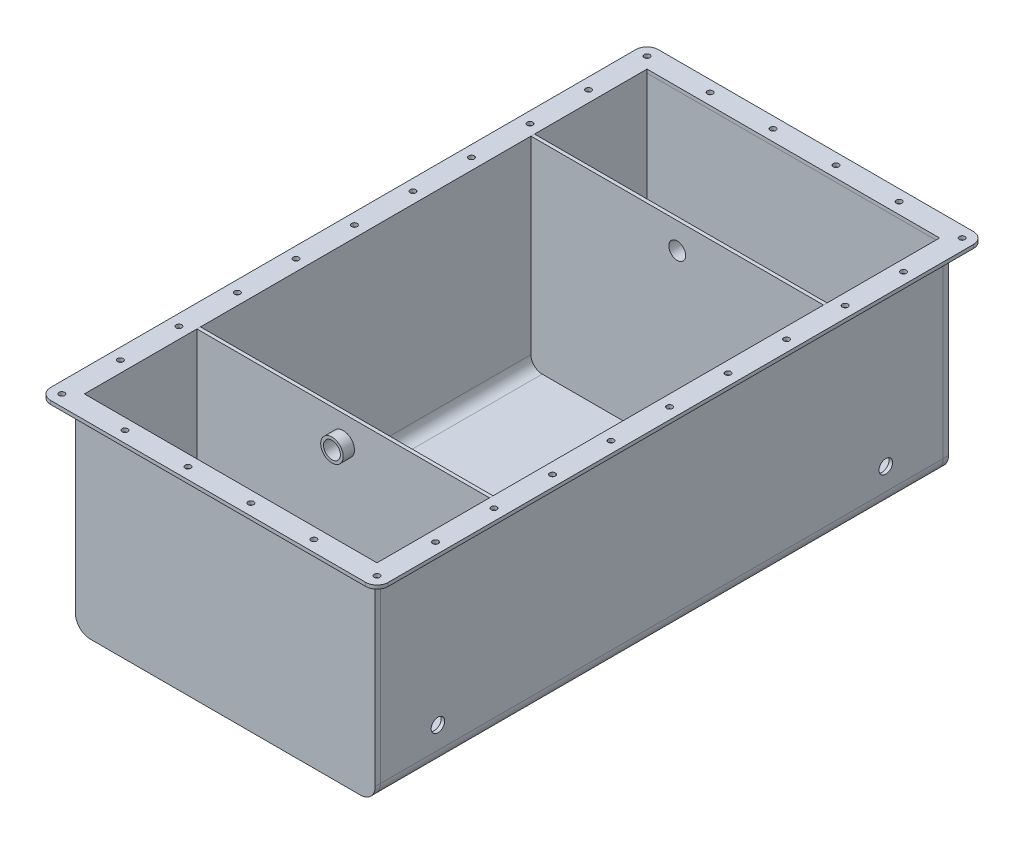
SolidWorks part; units mm, degrees
material "5052-H32"
ref_plane "Front Plane" through (0, 0, 0) normal (0, 0, 1) x (1, 0, 0)
ref_plane "Top Plane" through (0, 0, 0) normal (0, 1, 0) x (1, 0, 0)
ref_plane "Right Plane" through (0, 0, 0) normal (1, 0, 0) x (0, 0, -1)
sketch "Sketch2" plane through (0, 0, 0) normal (0, 0, 1) x (1, 0, 0)
  line L0 (-130, 0) -> (130, 0)
  line L1 (-130, 0) -> (-130, 175)
  line L2 (130, 0) -> (130, 175)
  line L3 (-133.175, -3.175) -> (-133.175, 175)
  line L4 (-133.175, -3.175) -> (133.175, -3.175)
  line L5 (133.175, -3.175) -> (133.175, 175)
  line L6 (-133.175, 175) -> (-130, 175)
  line L7 (130, 175) -> (133.175, 175)
  point P4 (0, 0)
  dimension "D1" = 260
  dimension "D3" = 175
  dimension "D4" = 175
  dimension "D2" = 3.175
  dimension "D5" = 3.175
  dimension "D6" = 3.175
extrude "Interior Dim" add sketch "Sketch2" against normal blind 500
fillet "Fillet2" radius 10 2 edges at (-130, 0, -250) (130, 0, -250)
fillet "Fillet3" radius 13.175 2 edges at (-133.175, -3.175, -250) (133.175, -3.175, -250)
ref_plane "Plane1" through (0, 0, 0) normal (0, 0, 1) x (1, 0, 0)
sketch "Sketch4" plane through (0, 0, 0) normal (0, 0, 1) x (1, 0, 0)
  line L0 (-130, 175) -> (130, 175)
  line L9 (-120, -3.175) -> (120, -3.175)
  line L10 (133.175, 10) -> (133.175, 175)
  line L11 (133.175, 175) -> (130, 175)
  line L12 (130, 175) -> (130, 10)
  line L13 (120, 0) -> (-120, 0)
  line L14 (-130, 10) -> (-130, 175)
  line L15 (-130, 175) -> (-133.175, 175)
  line L16 (-133.175, 175) -> (-133.175, 10)
  line L17 (-120, -3.175) -> (120, -3.175)
  line L18 (133.175, 10) -> (133.175, 175)
  line L19 (133.175, 175) -> (130, 175)
  line L23 (-130, 175) -> (-133.175, 175)
  line L24 (-133.175, 175) -> (-133.175, 10)
  arc A4 (120, -3.175) -> (133.175, 10) centre (120, 10) ccw
  arc A5 (120, 0) -> (130, 10) centre (120, 10) ccw
  arc A6 (-130, 10) -> (-120, 0) centre (-120, 10) ccw
  arc A7 (120, -3.175) -> (133.175, 10) centre (120, 10) ccw
  arc A9 (-133.175, 10) -> (-120, -3.175) centre (-120, 10) ccw
  arc A10 (-133.175, 10) -> (-120, -3.175) centre (-120, 10) ccw
  dimension "D1" = 0
extrude "Endcap1" add sketch "Sketch4" along normal blind 4.7625 separate body
ref_plane "Plane2" through (0, 0, -500) normal (0, 0, -1) x (-1, 0, 0)
sketch "Sketch5" plane through (0, 0, -500) normal (0, 0, -1) x (-1, 0, 0)
  line L8 (133.175, 175) -> (-133.175, 175)
  line L16 (-133.175, 175) -> (-133.175, 10)
  line L17 (-120, -3.175) -> (120, -3.175)
  line L18 (133.175, 10) -> (133.175, 175)
  line L19 (133.175, 175) -> (130, 175)
  line L20 (130, 175) -> (130, 10)
  line L21 (120, 0) -> (-120, 0)
  line L22 (-130, 10) -> (-130, 175)
  line L23 (-130, 175) -> (-133.175, 175)
  line L24 (-133.175, 175) -> (-133.175, 10)
  line L25 (-120, -3.175) -> (120, -3.175)
  line L26 (133.175, 10) -> (133.175, 175)
  arc A6 (-133.175, 10) -> (-120, -3.175) centre (-120, 10) ccw
  arc A7 (-133.175, 10) -> (-120, -3.175) centre (-120, 10) ccw
  arc A8 (120, 0) -> (130, 10) centre (120, 10) ccw
  arc A9 (-130, 10) -> (-120, 0) centre (-120, 10) ccw
  arc A12 (120, -3.175) -> (133.175, 10) centre (120, 10) ccw
  arc A13 (120, -3.175) -> (133.175, 10) centre (120, 10) ccw
  dimension "D1" = 0
ref_plane "Compartment1" through (0, 0, -100) normal (0, 0, -1) x (-1, 0, 0)
sketch "Sketch7" plane through (0, 0, -100) normal (0, 0, -1) x (-1, 0, 0)
  line L1 (130, 175) -> (-130, 175)
  line L10 (-120, -3.175) -> (120, -3.175)
  line L11 (-133.175, 175) -> (-133.175, 10)
  line L12 (-130, 175) -> (-133.175, 175)
  line L13 (-130, 10) -> (-130, 175)
  line L14 (120, 0) -> (-120, 0)
  line L15 (130, 175) -> (130, 10)
  line L16 (133.175, 175) -> (130, 175)
  line L17 (133.175, 10) -> (133.175, 175)
  line L21 (-130, 10) -> (-130, 175)
  line L22 (120, 0) -> (-120, 0)
  line L23 (130, 175) -> (130, 10)
  arc A5 (-130, 10) -> (-120, 0) centre (-120, 10) ccw
  arc A6 (120, 0) -> (130, 10) centre (120, 10) ccw
  arc A7 (-133.175, 10) -> (-120, -3.175) centre (-120, 10) ccw
  arc A8 (120, -3.175) -> (133.175, 10) centre (120, 10) ccw
  arc A9 (-130, 10) -> (-120, 0) centre (-120, 10) ccw
  arc A10 (120, 0) -> (130, 10) centre (120, 10) ccw
  dimension "D1" = 0
extrude "Compartment1_Boss" add sketch "Sketch7" along normal blind 3.175 separate body contours L22 A10 L23 L1 L21 A9 region at (0, 87.5805, -100)
ref_plane "Plane5" through (0, 175, 0) normal (0, 1, 0) x (1, 0, 0)
sketch "Sketch9" plane through (0, 175, 0) normal (0, 1, 0) x (1, 0, 0)
  line L0 (97.9962, 500) -> (-97.9962, 500) construction
  line L1 (-130, 500) -> (130, 500)
  line L2 (-130, 500) -> (-130, 0)
  line L3 (-130, 0) -> (130, 0)
  line L4 (130, 500) -> (130, 0)
  line L5 (-130, 0) -> (-130, 500) construction
  line L6 (-97.9962, 0) -> (97.9962, 0) construction
  line L7 (130, 500) -> (130, 0) construction
  line L8 (-150, 520) -> (-150, -20)
  line L9 (-150, -20) -> (150, -20)
  line L10 (150, 520) -> (150, -20)
  line L11 (-150, 520) -> (150, 520)
  circle A0 centre (-140, -10) radius 2.5
  circle A2 centre (-140, 42) radius 2.5
  circle A3 centre (-140, 94) radius 2.5
  circle A4 centre (-140, 146) radius 2.5
  circle A5 centre (-140, 198) radius 2.5
  circle A6 centre (-140, 250) radius 2.5
  circle A7 centre (-140, 302) radius 2.5
  circle A8 centre (-140, 354) radius 2.5
  circle A9 centre (-140, 406) radius 2.5
  circle A10 centre (-140, 458) radius 2.5
  circle A16 centre (-140, 510) radius 2.5
  circle A17 centre (-84, 510) radius 2.5
  circle A18 centre (-28, 510) radius 2.5
  circle A19 centre (28, 510) radius 2.5
  circle A20 centre (84, 510) radius 2.5
  circle A21 centre (140, 510) radius 2.5
  circle A22 centre (140, 458) radius 2.5
  circle A23 centre (140, 406) radius 2.5
  circle A24 centre (140, 354) radius 2.5
  circle A25 centre (140, 302) radius 2.5
  circle A26 centre (140, 250) radius 2.5
  circle A27 centre (140, 198) radius 2.5
  circle A28 centre (140, 146) radius 2.5
  circle A29 centre (140, 94) radius 2.5
  circle A30 centre (140, 42) radius 2.5
  circle A31 centre (140, -10) radius 2.5
  circle A37 centre (84, -10) radius 2.5
  circle A38 centre (28, -10) radius 2.5
  circle A39 centre (-28, -10) radius 2.5
  circle A40 centre (-84, -10) radius 2.5
  dimension "D4" = 5
  dimension "D7" = 5
  dimension "D2" = 10
  dimension "D3" = 10
  dimension "D5" = 6
  dimension "D6" = 11
  dimension "D8" = 11
  dimension "D1" = 20
extrude "Lid_Flange" add sketch "Sketch9" along normal blind 3.175 separate body contours L11 L8 L9 L10 A31 A21 A20 A19 A18 A17 A16 A10 A9 A8 A7 A6 A5 A4 A3 A2 A0 L1 L4 region at (0, 175, -513.8226)
fillet "Fillet4" radius 10 4 edges at (-150, 176.5875, -520) (150, 176.5875, -520) (150, 176.5875, 20) (-150, 176.5875, 20)
extrude "Endcap2" add sketch "Sketch5" along normal blind 4.7625 separate body
ref_plane "Compartment2" through (0, 0, -400) normal (0, 0, 1) x (1, 0, 0)
sketch "Sketch13" plane through (0, 0, -400) normal (0, 0, 1) x (1, 0, 0)
  line L0 (130, 175) -> (-130, 175)
  line L1 (133.175, 175) -> (130, 175) construction
  line L2 (130, 175) -> (130, 10) construction
  line L3 (-140, 175) -> (140, 175) construction
  line L4 (-130, 10) -> (-130, 175) construction
  line L5 (130, 175) -> (130, 10)
  line L6 (-130, 175) -> (-130, 10)
  line L7 (120, 0) -> (-120, 0)
  arc A0 (120, 0) -> (130, 10) centre (120, 10) ccw construction
  arc A1 (-130, 10) -> (-120, 0) centre (-120, 10) ccw construction
  arc A2 (-130, 10) -> (-120, 0) centre (-120, 10) ccw
  arc A3 (130, 10) -> (120, 0) centre (120, 10) cw
  dimension "D1" = 175
extrude "Compartment2_Boss" add sketch "Sketch13" along normal blind 3.175
sketch "Sketch16" plane through (-133.175, 0, 0) normal (-1, 0, 0) x (0, 0, 1)
  line L0 (-500, 0) -> (-400, 0) construction
  line L1 (-500, 175) -> (-500, 10) construction
  line L2 (0, 175) -> (0, 10) construction
  line L3 (-51, 29.5) -> (-449, 29.5) construction
  circle A0 centre (-449, 29.5) radius 6
  circle A1 centre (-51, 29.5) radius 6
  dimension "D1" = 12
  dimension "D4" = 12
  dimension "D2" = 29.5
  dimension "D3" = 51
  dimension "D5" = 51
extrude "Bearing_holes" cut sketch "Sketch16" against normal through all
sketch "Sketch17" plane through (0, 0, -400) normal (0, 0, -1) x (-1, 0, 0)
  line L0 (142.7388, 175) -> (-142.7388, 175) construction
  line L1 (130, 175) -> (130, 10) construction
  circle A0 centre (0, 155) radius 7.5
  circle A1 centre (0, 155) radius 10
  dimension "D1" = 15
  dimension "D4" = 20
  dimension "D2" = 20
  dimension "D3" = 130
extrude "Wire_Passthrough" cut sketch "Sketch17" against normal up to surface (300 mm away) contours A0 region at (0, 155, -400) up to face at (0, 60.9763, -100)
sketch "Sketch18" plane through (0, 175, 0) normal (0, 1, 0) x (1, 0, 0)
  line L1 (-130, 400) -> (130, 400)
  line L2 (-130, 400) -> (-130, 396.825)
  line L3 (-130, 396.825) -> (130, 396.825)
  line L4 (130, 400) -> (130, 396.825)
  line L5 (-130, 103.175) -> (130, 103.175)
  line L6 (-130, 103.175) -> (-130, 100)
  line L7 (-130, 100) -> (130, 100)
  line L8 (130, 103.175) -> (130, 100)
extrude "Boss-Extrude1" add sketch "Sketch18" along normal blind 3.18
extrude "Wire_Tube_2" add sketch "Sketch17<3>" along normal blind 10
sketch "Sketch17<3>" plane through (0, 0, -400) normal (0, 0, -1) x (-1, 0, 0) same geometry as "Sketch17"
sketch "Sketch19" plane through (0, 0, -100) normal (0, 0, 1) x (1, 0, 0)
  circle A0 centre (0, 155) radius 10
  circle M1 centre (0, 155) radius 7.5
  dimension "D1" = 20
extrude "Wire_Tube_1" add sketch "Sketch19" along normal blind 10 contours A0 M1 region at (-9.7172, 155, -100)
equation "\"L\"= 500"
equation "\"W\"= 260"
equation "\"D1@Sketch2\"=\"W\""
equation "\"D1@Interior Dim\" = \"L\""
equation "\"H\"= 175"
equation "\"D3@Sketch2\"=\"H\""
equation "\"D4@Sketch2\"=\"H\""
equation "\"Compartment Width\"= 100"
equation "\"D1@Compartment2\"=\"Compartment Width\""
equation "\"D1@Compartment1\"=\"Compartment Width\""
equation "\"D1@Sketch13\"=\"H\""
equation "\"D3@Sketch17\"=\"W\"/2"
equation "\"T\"= 4.7625 * 2 / 3"
equation "\"D1@Lid_Flange\"=\"T\""
equation "\"D1@Fillet3\"=\"T\"+10"
equation "\"D1@Compartment1_Boss\"=\"T\""
equation "\"D1@Compartment2_Boss\"=\"T\""
